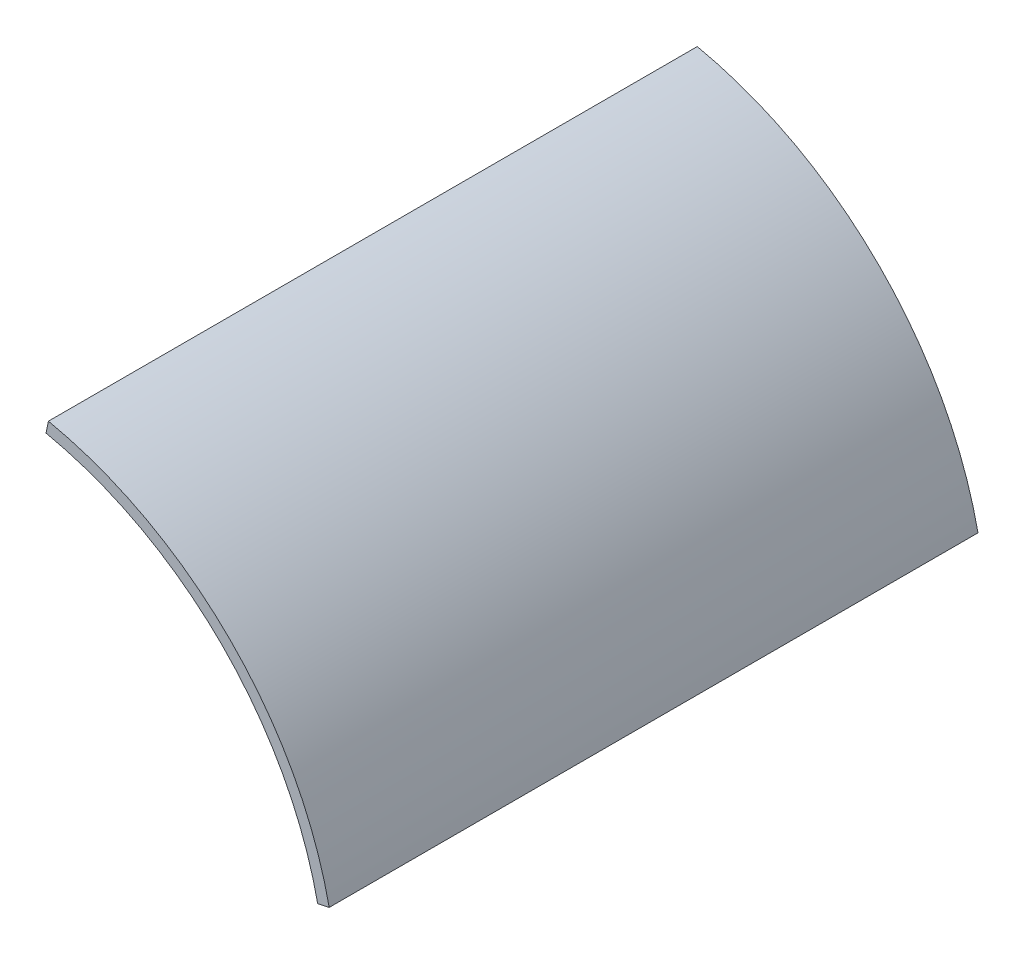
SolidWorks part; units mm, degrees
material "ABS"
ref_plane "Alzado" through (0, 0, 0) normal (0, 0, 1) x (1, 0, 0)
ref_plane "Planta" through (0, 0, 0) normal (0, 1, 0) x (1, 0, 0)
ref_plane "Vista lateral" through (0, 0, 0) normal (1, 0, 0) x (0, 0, -1)
sketch "Croquis1" plane through (0, 0, 0) normal (0, 0, 1) x (1, 0, 0)
  line L0 (0, 0) -> (0, 58) construction
  line L1 (0, 0) -> (58, 0) construction
  line L2 (0, 0) -> (30.2248, 6.4245) construction
  line L3 (0, 0) -> (6.4245, 30.2248) construction
  line L4 (6.4245, 30.2248) -> (6.2166, 29.2466)
  line L5 (30.2248, 6.4245) -> (29.2466, 6.2166)
  arc A0 (6.2166, 29.2466) -> (29.2466, 6.2166) centre (0, 0) cw
  arc A1 (30.2248, 6.4245) -> (6.4245, 30.2248) centre (0, 0) ccw
  dimension "D1" = 29.9
  dimension "D2" = 1
  dimension "D3" = 12
  dimension "D4" = 12
extrude "Saliente-Extruir1" add sketch "Croquis1" along normal blind 55
